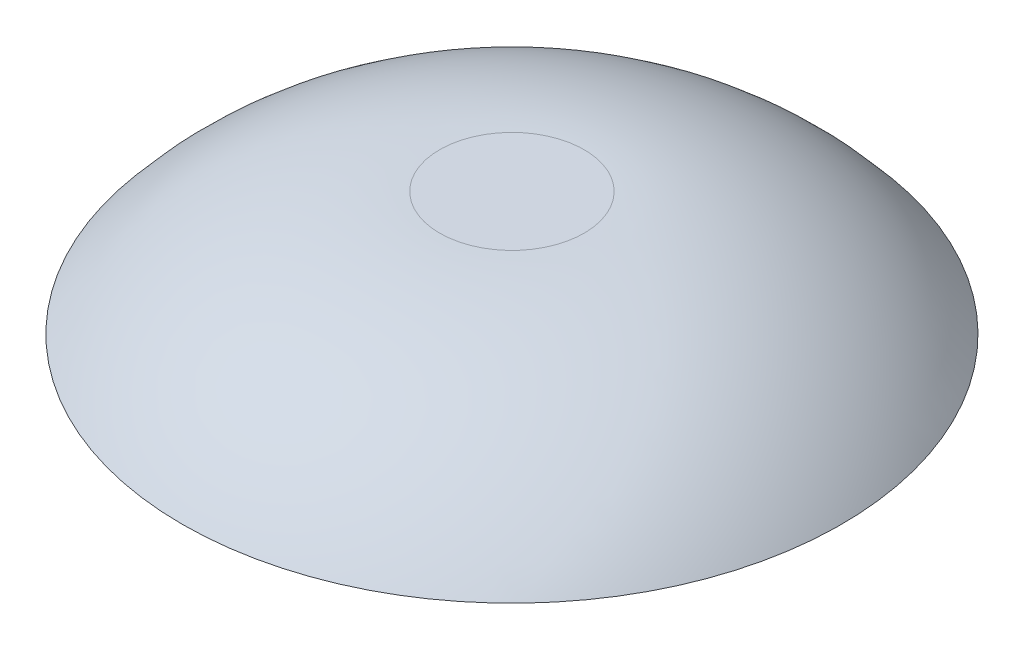
SolidWorks part; units mm, degrees
ref_plane "Front Plane" through (0, 0, 0) normal (0, 0, 1) x (1, 0, 0)
ref_plane "Top Plane" through (0, 0, 0) normal (0, 1, 0) x (1, 0, 0)
ref_plane "Right Plane" through (0, 0, 0) normal (1, 0, 0) x (0, 0, -1)
sketch "Sketch1" plane through (0, 0, 0) normal (0, 1, 0) x (1, 0, 0)
  circle A0 centre (0, 0) radius 20
  dimension "D1" = 40
extrude "Boss-Extrude1" add sketch "Sketch1" along normal blind 7.5
fillet "Fillet1" radius 20 1 edges at (0, 7.5, 20)
sketch "Sketch2" plane through (0, 0, 0) normal (0, -1, 0) x (1, 0, 0)
  line L0 (4.125, 0) -> (-4.125, 0) construction
  line L1 (3.1, 1.7898) -> (0, 3.5796)
  line L2 (0, 3.5796) -> (-3.1, 1.7898)
  line L3 (-3.1, 1.7898) -> (-3.1, -1.7898)
  line L4 (-3.1, -1.7898) -> (0, -3.5796)
  line L5 (0, -3.5796) -> (3.1, -1.7898)
  line L6 (3.1, -1.7898) -> (3.1, 1.7898)
  circle A0 centre (0, 0) radius 3.1 construction
  circle A1 centre (0, 0) radius 6.925
  dimension "D2" = 13.85
  dimension "D1" = 3.1
extrude "Cut-Extrude1" cut sketch "Sketch2" against normal blind 7 contours A1 L6 L5 L4 L3 L2 L1 region at (-6.7291, 0, 0)
sketch "Sketch3" plane through (0, 0, 0) normal (0, -1, 0) x (1, 0, 0)
  circle A0 centre (0, 0) radius 4.5582
extrude "Cut-Extrude2" cut sketch "Sketch3" against normal blind 2.5 contours A0
ref_plane "Plane1" through (0, 0, 15) normal (0, 0, 1) x (1, 0, 0)
sketch "Sketch5" plane through (0, 0, 15) normal (0, 0, 1) x (1, 0, 0)
  line L1 (2.5, -1.5) -> (-2.5, -1.5)
  line L2 (2.5, -1.5) -> (2.5, 1.5)
  line L3 (2.5, 1.5) -> (-2.5, 1.5)
  line L4 (-2.5, -1.5) -> (-2.5, 1.5)
  line L5 (2.5, -1.5) -> (-2.5, 1.5) construction
  line L6 (2.5, 1.5) -> (-2.5, -1.5) construction
  point P0 (0, 0)
  dimension "D1" = 3
  dimension "D2" = 5
